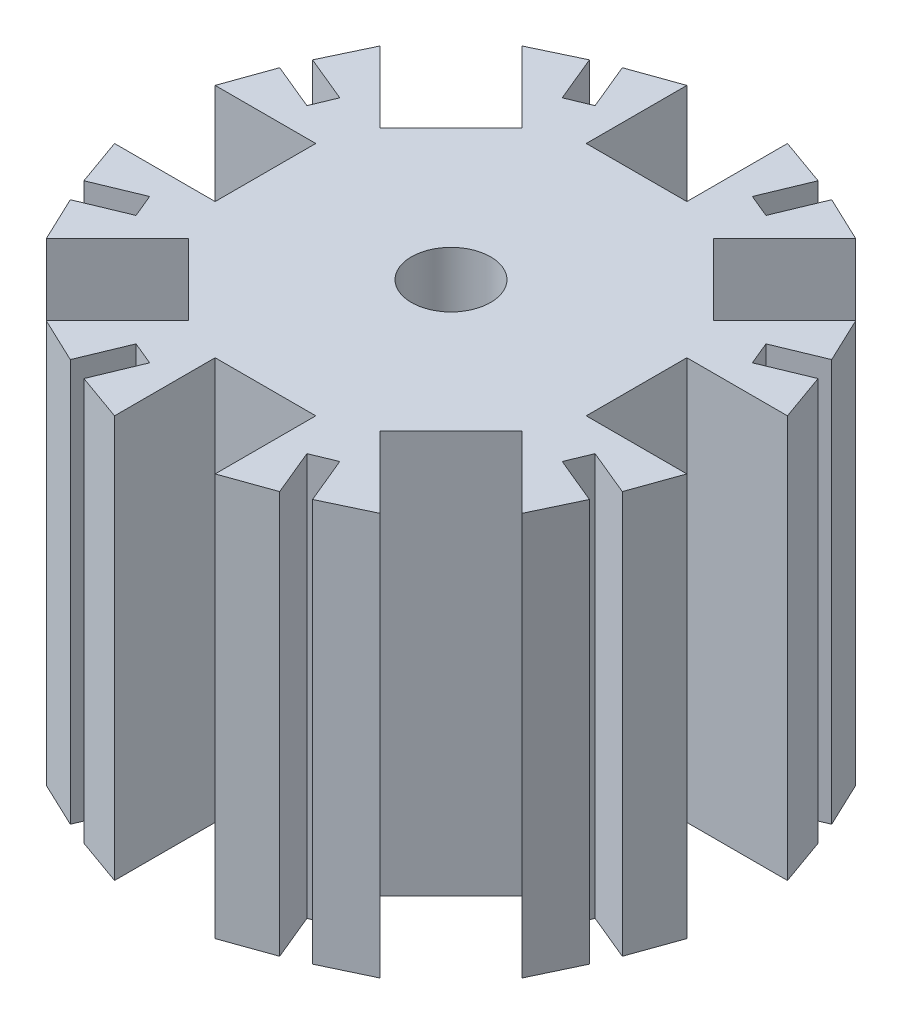
SolidWorks part; units mm, degrees
ref_plane "Front Plane" through (0, 0, 0) normal (0, 0, 1) x (1, 0, 0)
ref_plane "Top Plane" through (0, 0, 0) normal (0, 1, 0) x (1, 0, 0)
ref_plane "Right Plane" through (0, 0, 0) normal (1, 0, 0) x (0, 0, -1)
sketch "Sketch1" plane through (0, 0, 0) normal (0, 1, 0) x (1, 0, 0)
  line L0 (0, 0) -> (36.1226, 0) construction
  line L1 (0, 0) -> (25.5425, 25.5425) construction
  line L2 (25.5425, 25.5425) -> (21.0524, 30.0327) construction
  line L3 (21.0524, 30.0327) -> (12.0722, 21.0524)
  line L4 (12.0722, 21.0524) -> (21.0524, 12.0722)
  line L5 (21.0524, 12.0722) -> (30.0327, 21.0524)
  line L6 (0, 0) -> (33.3729, 13.8235) construction
  line L7 (33.3729, 13.8235) -> (32.7654, 15.2902) construction
  line L8 (32.7654, 15.2902) -> (26.8988, 12.8601)
  line L9 (26.8988, 12.8601) -> (28.1138, 9.9268)
  line L10 (28.1138, 9.9268) -> (33.9804, 12.3569)
  line L11 (30.0327, 21.0524) -> (32.7654, 15.2902)
  line L12 (36.1226, 0) -> (36.1226, 6.35) construction
  line L13 (33.9804, 12.3569) -> (36.1226, 6.35)
  line L16 (36.1226, 6.35) -> (23.4226, 6.35) construction
  line L17 (0, 0) -> (12.0722, 21.0524)
  line L18 (23.4226, 6.35) -> (0, 0)
  line L19 (23.4226, 6.35) -> (36.1226, 6.35)
  arc A0 (2.4872, 4.3375) -> (4.8258, 1.3083) centre (0, 0) cw
  dimension "D15" = 5
  dimension "D1" = 36.1226
  dimension "D2" = 36.1226
  dimension "D4" = 6.35
  dimension "D5" = 12.7
  dimension "D6" = 12.7
  dimension "D7" = 36.1226
  dimension "D9" = 1.5875
  dimension "D10" = 6.35
  dimension "D11" = 3.175
  dimension "D12" = 6.35
  dimension "D13" = 6.35
  dimension "D3" = 22.5
  dimension "D8" = 22.5
  dimension "D14" = 12.7
extrude "Boss-Extrude3" add sketch "Sketch1" along normal blind 50.8 contours L13 L10 L9 L8 L11 L5 L4 region at (18.095, 0, -10.4181)
ref_axis "Axis1" through (0, -0.25, 0) along (0, 1, 0)
pattern_circular "CirPattern2" count 8 over 360 about axis through (0, -0.25, 0) along (0, 1, 0) of bodies 103
combine bodies "Combine2" operation type add bodies to combine 111 112 113 114 115 116 117 103
equation "\"R\"= 2.8443 / 2'Outer Radius"
equation "\"d\"= 10 / 25.4'Inner Diameter"
equation "\"L_w\"= 0.5'Large Magnet Width"
equation "\"L_l\"= 0.5'Large Magnet Length"
equation "\"S_w\"= 0.125'Small Magnet Width"
equation "\"S_l\"= 0.25'Small Magnet Length"
equation "\"D1@Sketch1\"=\"R\""
equation "\"D2@Sketch1\"=\"R\""
equation "\"D4@Sketch1\"=\"L_w\"/2"
equation "\"D5@Sketch1\"=\"L_l\""
equation "\"D6@Sketch1\"=\"L_w\""
equation "\"D7@Sketch1\"=\"R\""
equation "\"D9@Sketch1\"=\"S_w\"/2"
equation "\"D10@Sketch1\"=\"S_l\""
equation "\"D11@Sketch1\"=\"S_w\""
equation "\"D12@Sketch1\"=\"S_l\""
equation "\"D13@Sketch1\"=\"L_w\"/2"
equation "\"N\"= 8'Instances"
equation "\"D3@Sketch1\"=360/(\"N\"*2)"
equation "\"D8@Sketch1\"=360/(\"N\"*2)"
equation "\"D1@CirPattern1\"=\"N\""
equation "\"D14@Sketch1\"=\"L_l\""
equation "\"D1@CirPattern2\"=\"N\""
equation "\"D15@Sketch1\"=\"d\"/2"
